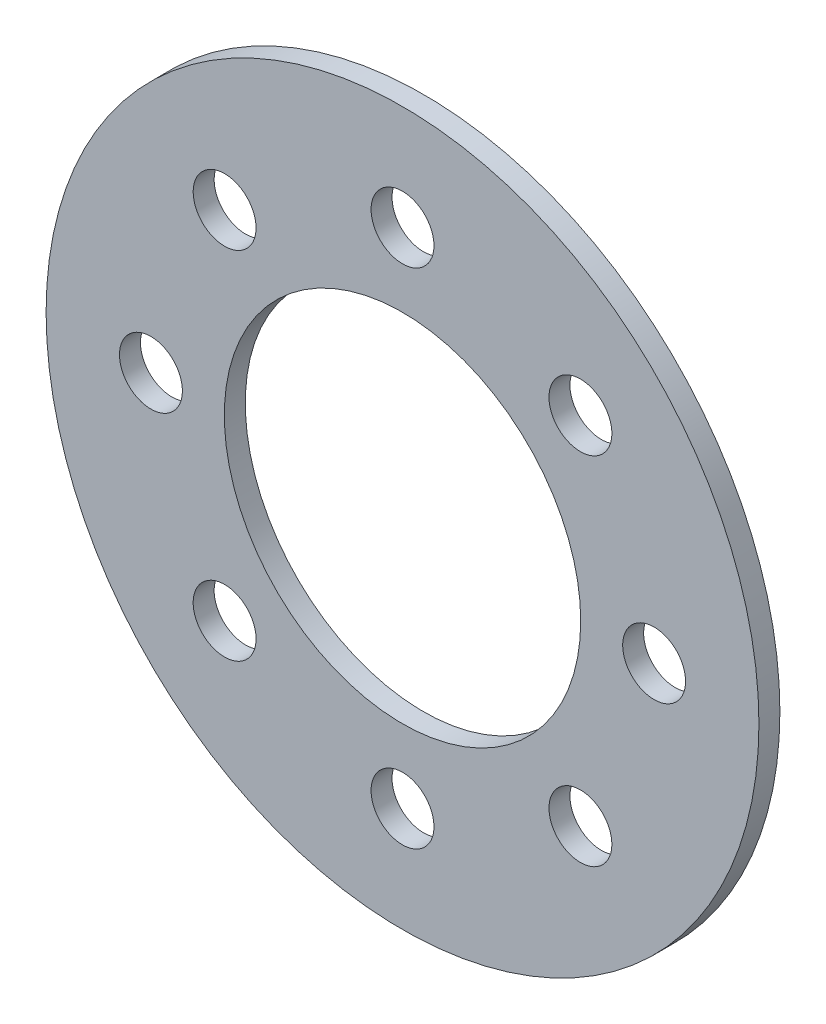
SolidWorks part; units mm, degrees
material "PLA 50%"
ref_plane "Front Plane" through (0, 0, 0) normal (0, 0, 1) x (1, 0, 0)
ref_plane "Top Plane" through (0, 0, 0) normal (0, 1, 0) x (1, 0, 0)
ref_plane "Right Plane" through (0, 0, 0) normal (1, 0, 0) x (0, 0, -1)
ref_axis "X" through (-88.99, 0, 0) along (1, 0, 0)
ref_axis "Y" through (0, 55, 0) along (0, -1, 0)
ref_axis "Z" through (0, 0, -88.99) along (0, 0, 1)
sketch "Sketch1" plane through (0, 0, 0) normal (0, 0, 1) x (1, 0, 0)
  circle A0 centre (0, 0) radius 8.5
  circle A1 centre (0, 0) radius 17
  dimension "D1" = 34
  dimension "D2" = 17
extrude "Boss-Extrude1" add sketch "Sketch1" along normal blind 1
sketch "Sketch2" plane through (0, 0, 1) normal (0, 0, 1) x (1, 0, 0)
  circle A0 centre (0, 12) radius 1.5
  dimension "D1" = 3
  dimension "D2" = 12
extrude "Cut-Extrude1" cut sketch "Sketch2" against normal through all both
pattern_circular "CirPattern1" count 8 over 360 about axis through (0, 0, 1) along (0, 0, -1) of "Cut-Extrude1"
